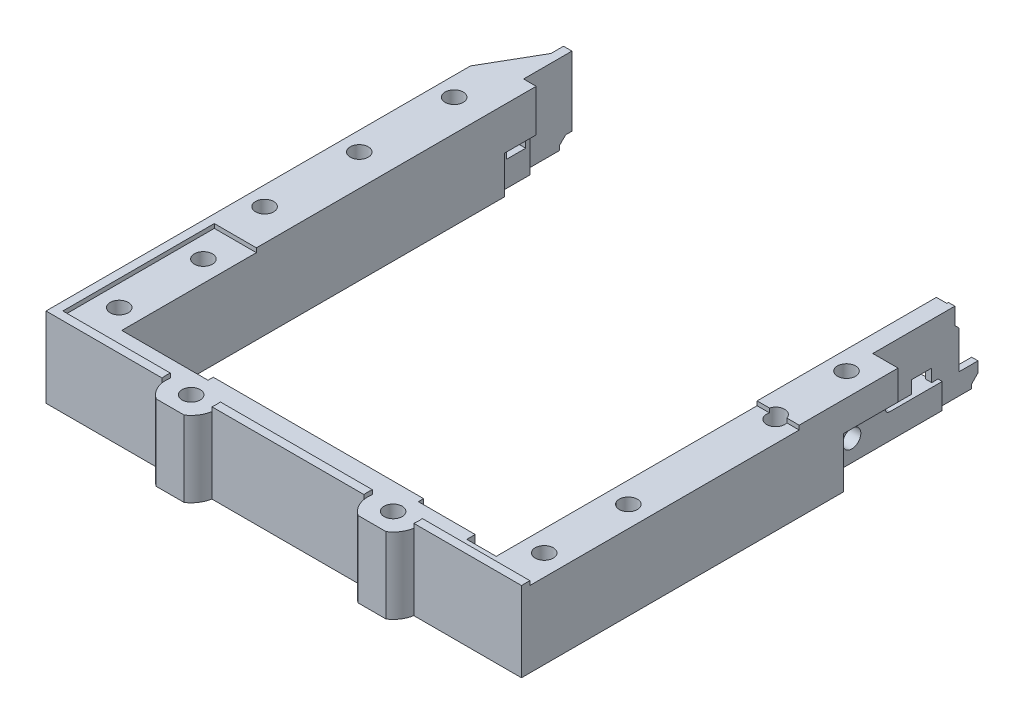
SolidWorks part; units mm, degrees
ref_plane "前视基准面" through (0, 0, 0) normal (0, 0, 1) x (1, 0, 0)
ref_plane "上视基准面" through (0, 0, 0) normal (0, 1, 0) x (1, 0, 0)
ref_plane "右视基准面" through (0, 0, 0) normal (1, 0, 0) x (0, 0, -1)
sketch "草图2" plane through (0, 0, 0) normal (0, 1, 0) x (1, 0, 0)
  line L0 (0, 0) -> (0, -10) construction
  line L1 (-45.5, 0) -> (45.5, 0)
  line L2 (45.5, 0) -> (45.5, 93)
  line L3 (45.5, 93) -> (55.5, 93)
  line L4 (55.5, 93) -> (55.5, -10)
  line L5 (55.5, -10) -> (-55.5, -10)
  line L6 (-45.5, 93) -> (-55.5, 93)
  line L7 (-55.5, 93) -> (-55.5, -10)
  line L8 (-45.5, 0) -> (-45.5, 93)
  dimension "D1" = 10
  dimension "D2" = 10
  dimension "D3" = 45.5
  dimension "D4" = 93
extrude "凸台-拉伸1" add sketch "草图2" along normal blind 18
sketch "草图3" plane through (0, 18, 0) normal (0, 1, 0) x (1, 0, 0)
  line L0 (55.5, 93) -> (45.5, 93) construction
  line L1 (45.5, 93) -> (45.5, 0) construction
  circle A0 centre (50, 76.75) radius 2.15
  dimension "D1" = 16.25
  dimension "D2" = 4.3
  dimension "D3" = 4.5
extrude "切除-拉伸1" cut sketch "草图3" against normal through all
sketch "草图4" plane through (55.5, 0, 0) normal (1, 0, 0) x (0, 0, -1)
  line L0 (-10, 0) -> (93, 0) construction
  line L1 (93, 18) -> (85.5, 18)
  line L2 (93, 18) -> (93, 0)
  line L3 (93, 0) -> (85.5, 0)
  line L4 (85.5, 18) -> (85.5, 0)
  line L5 (93, 18) -> (85.5, 0) construction
  line L6 (93, 0) -> (85.5, 18) construction
  point P4 (89.25, 9)
  dimension "D1" = 7.5
extrude "切除-拉伸2" cut sketch "草图4" against normal blind 6
sketch "草图5" plane through (55.5, 0, 0) normal (1, 0, 0) x (0, 0, -1)
  line L0 (85.5, 18) -> (85.5, 0) construction
  line L1 (85.5, 12) -> (70.5, 12)
  line L2 (85.5, 12) -> (85.5, 0)
  line L3 (85.5, 0) -> (70.5, 0)
  line L4 (70.5, 12) -> (70.5, 0)
  line L5 (85.5, 12) -> (70.5, 0) construction
  line L6 (85.5, 0) -> (70.5, 12) construction
  line L7 (-10, 0) -> (85.5, 0) construction
  line L8 (-10, 18) -> (85.5, 18) construction
  point P4 (78, 6)
  dimension "D1" = 6
  dimension "D2" = 15
extrude "切除-拉伸3" cut sketch "草图5" against normal up to surface (6 mm away) up to face at (49.5, 9, -89.25)
sketch "草图6" plane through (49.5, 0, 0) normal (1, 0, 0) x (0, 0, -1)
  line L1 (93, 0) -> (91, 0)
  line L2 (93, 0) -> (93, 9)
  line L3 (93, 9) -> (91, 9)
  line L4 (91, 0) -> (91, 9)
  line L5 (93, 0) -> (91, 9) construction
  line L6 (93, 9) -> (91, 0) construction
  point P4 (92, 4.5)
  dimension "D1" = 9
  dimension "D2" = 2
extrude "切除-拉伸4" cut sketch "草图6" against normal up to next
sketch "草图7" plane through (0, 18, 0) normal (0, 1, 0) x (1, 0, 0)
  line L0 (-45.5, 0) -> (-45.5, 93) construction
  line L1 (-55.5, 93) -> (-45.5, 93)
  line L2 (-55.5, 93) -> (-55.5, 32)
  line L3 (-55.5, 32) -> (-45.5, 32)
  line L4 (-45.5, 93) -> (-45.5, 32)
  line L5 (-55.5, 93) -> (-45.5, 32) construction
  line L6 (-55.5, 32) -> (-45.5, 93) construction
  point P4 (-50.5, 62.5)
  dimension "D1" = 61
extrude "凸台-拉伸2" add sketch "草图7" along normal blind 1
sketch "草图8" plane through (-55.5, 0, 0) normal (-1, 0, 0) x (0, 0, 1)
  line L1 (-32, 19) -> (-93, 19)
  line L2 (-32, 19) -> (-32, 0)
  line L3 (-32, 0) -> (-93, 0)
  line L4 (-93, 19) -> (-93, 0)
  line L5 (-32, 19) -> (-93, 0) construction
  line L6 (-32, 0) -> (-93, 19) construction
  point P4 (-62.5, 9.5)
extrude "凸台-拉伸3" add sketch "草图8" along normal blind 4
sketch "草图9" plane through (-55.5, 0, 0) normal (-1, 0, 0) x (0, 0, 1)
  line L1 (10, 0) -> (-32, 0)
  line L2 (10, 0) -> (10, 19)
  line L3 (10, 19) -> (-32, 19)
  line L4 (-32, 0) -> (-32, 19)
  line L5 (10, 0) -> (-32, 19) construction
  line L6 (10, 19) -> (-32, 0) construction
  point P4 (-11, 9.5)
extrude "凸台-拉伸4" add sketch "草图9" along normal blind 2
sketch "草图10" plane through (0, 18, 0) normal (0, 1, 0) x (1, 0, 0)
  line L0 (-57.5, -10) -> (-57.5, 32) construction
  line L1 (-55.5, -10) -> (55.5, -10) construction
  circle A0 centre (-50.5, 4.4) radius 2.15
  circle A1 centre (-50.5, 24.4) radius 2.15
  circle A2 centre (-24, -5) radius 2.15
  circle A3 centre (24, -5) radius 2.15
  dimension "D1" = 4.3
  dimension "D2" = 7
  dimension "D3" = 14.4
  dimension "D4" = 20
  dimension "D5" = 5
  dimension "D6" = 33.5
  dimension "D7" = 48
extrude "切除-拉伸5" cut sketch "草图10" against normal blind 6
sketch "草图11" plane through (0, 0, 0) normal (0, 0, -1) x (-1, 0, 0)
  line L0 (-45.5, 18) -> (45.5, 18) construction
  line L1 (-25, 18) -> (25, 18)
  line L2 (-25, 18) -> (-25, 0)
  line L3 (-25, 0) -> (25, 0)
  line L4 (25, 18) -> (25, 0)
  line L5 (-25, 18) -> (25, 0) construction
  line L6 (-25, 0) -> (25, 18) construction
  line L7 (-45.5, 0) -> (45.5, 0) construction
  point P4 (0, 9)
  dimension "D1" = 50
extrude "凸台-拉伸5" add sketch "草图11" along normal blind 1.25
sketch "草图12" plane through (0, 18, 0) normal (0, 1, 0) x (1, 0, 0)
  line L0 (49.5, 93) -> (45.5, 93)
  line L1 (45.5, 93) -> (45.5, 60)
  line L2 (45.5, 93) -> (45.5, 0) construction
  line L3 (45.5, 60) -> (55.5, 60)
  line L4 (55.5, -10) -> (55.5, 85.5) construction
  line L5 (55.5, 60) -> (55.5, 85.5)
  line L6 (55.5, 85.5) -> (49.5, 85.5)
  line L7 (49.5, 85.5) -> (49.5, 93)
  circle A0 centre (50, 76.75) radius 2.15 construction
  circle A1 centre (50, 76.75) radius 2.15
  dimension "D1" = 33
extrude "凸台-拉伸6" add sketch "草图12" along normal blind 1
sketch "草图13" plane through (0, 18, 0) normal (0, 1, 0) x (1, 0, 0)
  line L1 (45.5, 0) -> (38.5, 0)
  line L2 (45.5, 0) -> (45.5, -2)
  line L3 (45.5, -2) -> (38.5, -2)
  line L4 (38.5, 0) -> (38.5, -2)
  line L5 (45.5, 0) -> (38.5, -2) construction
  line L6 (45.5, -2) -> (38.5, 0) construction
  point P4 (42, -1)
  dimension "D1" = 7
  dimension "D2" = 2
extrude "切除-拉伸6" cut sketch "草图13" against normal up to surface (18 mm away) up to face at (4.075, 0, -39.3889)
sketch "草图14" plane through (0, 18, 0) normal (0, 1, 0) x (1, 0, 0)
  line L0 (55.5, -10) -> (55.5, 60) construction
  line L1 (-57.5, -10) -> (-27.3166, -10)
  line L2 (-57.5, -10) -> (-57.5, -6)
  line L3 (-57.5, -6) -> (-29.9161, -6)
  line L4 (55.5, -10) -> (55.5, -6)
  line L5 (-18.0839, -6) -> (18.0839, -6)
  line L6 (-20.6834, -10) -> (20.6834, -10)
  line L7 (29.9161, -6) -> (55.5, -6)
  line L8 (27.3166, -10) -> (55.5, -10)
  arc A0 (-29.9161, -6) -> (-27.3166, -10) centre (-24, -5) ccw
  arc A1 (18.0839, -6) -> (20.6834, -10) centre (24, -5) ccw
  arc A2 (-20.6834, -10) -> (-18.0839, -6) centre (-24, -5) ccw
  arc A3 (27.3166, -10) -> (29.9161, -6) centre (24, -5) ccw
  dimension "D2" = 12
  dimension "D3" = 12
  dimension "D1" = 4
extrude "切除-拉伸7" cut sketch "草图14" against normal through all and the other way through all
sketch "草图16" plane through (0, 18, 0) normal (0, 1, 0) x (1, 0, 0)
  line L0 (55.5, -6) -> (55.5, 60) construction
  line L1 (-55.5, -6) -> (-29.9161, -6)
  line L2 (-55.5, -6) -> (-55.5, -4)
  line L3 (-55.5, -4) -> (-29.9161, -4)
  line L4 (55.5, -6) -> (55.5, -4)
  line L5 (-18.0839, -4) -> (18.0839, -4)
  line L6 (-18.0839, -6) -> (18.0839, -6)
  line L7 (29.9161, -4) -> (55.5, -4)
  line L8 (29.9161, -6) -> (55.5, -6)
  arc A0 (-29.9161, -4) -> (-29.9161, -6) centre (-24, -5) ccw
  arc A1 (18.0839, -4) -> (18.0839, -6) centre (24, -5) ccw
  arc A2 (-18.0839, -6) -> (-18.0839, -4) centre (-24, -5) ccw
  arc A3 (29.9161, -6) -> (29.9161, -4) centre (24, -5) ccw
  dimension "D1" = 2
extrude "凸台-拉伸7" add sketch "草图16" along normal up to surface (1 mm away) up to face at (-54.5, 19, -37.75)
sketch "草图18" plane through (0, 19, 0) normal (0, 1, 0) x (1, 0, 0)
  line L0 (-53, 86.45) -> (-53, 41.45) construction
  line L1 (-59.5, 32) -> (-59.5, 93) construction
  line L2 (-45.5, 93) -> (-59.5, 93) construction
  circle A0 centre (-53, 86.45) radius 2.15
  circle A1 centre (-53, 63.95) radius 2.15
  circle A2 centre (-53, 41.45) radius 2.15
  dimension "D1" = 4.3
  dimension "D2" = 6.5
  dimension "D3" = 6.55
  dimension "D4" = 45
extrude "切除-拉伸8" cut sketch "草图18" against normal blind 6
sketch "草图19" plane through (0, 12, 0) normal (0, 1, 0) x (1, 0, 0)
  circle A0 centre (24, -5) radius 2.15 construction
  circle A1 centre (-24, -5) radius 2.15 construction
  circle A2 centre (24, -5) radius 2.15
  circle A3 centre (-24, -5) radius 2.15
extrude "切除-拉伸9" cut sketch "草图19" against normal through all
sketch "草图20" plane through (0, 13, 0) normal (0, 1, 0) x (1, 0, 0)
  line L0 (0, 0) -> (0, 86.45) construction
  circle A0 centre (-50.5, 4.4) radius 2.15 construction
  circle A1 centre (-50.5, 24.4) radius 2.15 construction
  circle A2 centre (-53, 41.45) radius 2.15 construction
  circle A3 centre (-53, 63.95) radius 2.15 construction
  circle A4 centre (-53, 86.45) radius 2.15 construction
  circle A5 centre (-50.5, 4.4) radius 2.15
  circle A6 centre (-50.5, 24.4) radius 2.15
  circle A7 centre (-53, 41.45) radius 2.15
  circle A8 centre (-53, 63.95) radius 2.15
  circle A9 centre (-53, 86.45) radius 2.15
  circle A10 centre (50.5, 24.4) radius 2.15
  circle A11 centre (50.5, 4.4) radius 2.15
extrude "切除-拉伸10" cut sketch "草图20" against normal through all and the other way through all
sketch "草图21" plane through (0, 0, 0) normal (0, -1, 0) x (1, 0, 0)
  line L1 (-45.5, -93) -> (45.5, -93)
  line L2 (-45.5, -93) -> (-45.5, 2)
  line L3 (-45.5, 2) -> (45.5, 2)
  line L4 (45.5, -93) -> (45.5, 2)
extrude "凸台-拉伸8" [suppressed] add sketch "草图21" against normal blind 2
sketch "草图22" [suppressed] plane through (0, 2, 0) normal (0, 1, 0) x (1, 0, 0)
  line L1 (38.5, 0) -> (45.5, 0)
  line L2 (38.5, 0) -> (38.5, -2)
  line L3 (38.5, -2) -> (45.5, -2)
  line L4 (45.5, 0) -> (45.5, -2)
extrude "凸台-拉伸9" [suppressed] add sketch "草图22" along normal blind 15
sketch "草图23" plane through (0, 0, -32) normal (0, 0, 1) x (1, 0, 0)
  line L4 (-59.5, 0) -> (-57.5, 0)
  line L5 (-57.5, 0) -> (-57.5, 19)
  line L6 (-57.5, 19) -> (-59.5, 19)
  line L7 (-59.5, 19) -> (-59.5, 0)
  line L8 (-59.5, 0) -> (-57.5, 0)
  line L9 (-57.5, 0) -> (-57.5, 19)
  line L10 (-57.5, 19) -> (-59.5, 19)
  line L11 (-59.5, 19) -> (-59.5, 0)
  dimension "D1" = 0
extrude "切除-拉伸11" cut sketch "草图23" against normal through all
sketch "草图24" plane through (0, 19, 0) normal (0, 1, 0) x (1, 0, 0)
  line L0 (-45.5, 93) -> (-49.5, 93)
  line L1 (-45.5, 93) -> (-57.5, 93) construction
  line L2 (-49.5, 93) -> (-45.5, 89)
  line L3 (-45.5, 32) -> (-45.5, 93) construction
  line L4 (-45.5, 89) -> (-45.5, 93)
  dimension "D1" = 4
  dimension "D2" = 4
sketch "草图26" plane through (49.5, 0, 0) normal (1, 0, 0) x (0, 0, -1)
  line L0 (91, 0) -> (91, 6)
  line L2 (91, 9) -> (91, 0) construction
  line L3 (91, 6) -> (98, 6)
  line L4 (98, 6) -> (98, 9)
  line L5 (98, 9) -> (93, 9)
  line L6 (93, 9) -> (93, 19)
  line L7 (93, 19) -> (107, 19)
  line L8 (107, 19) -> (107, 0)
  line L9 (107, 0) -> (91, 0)
  dimension "D1" = 6
  dimension "D2" = 5
  dimension "D3" = 16
extrude "凸台-拉伸10" add sketch "草图26" against normal offset from surface (3 mm away) 1 contours L8 L9 L0 L3 L4 L5 L6 L7 up to face at (45.5, 11.5, -60.5)
sketch "草图27" plane through (46.5, 0, 0) normal (-1, 0, 0) x (0, 0, 1)
  line L0 (-98, 13) -> (-98, 0)
  line L1 (-91, 0) -> (-107, 0) construction
  line L2 (-98, 0) -> (-107, 0)
  line L3 (-107, 0) -> (-107, 19)
  line L4 (-98, 9) -> (-98, 6) construction
  line L5 (-93, 9) -> (-98, 9) construction
  line L6 (-98, 13) -> (-101.4641, 19)
  line L7 (-107, 19) -> (-93, 19) construction
  line L8 (-107, 19) -> (-101.4641, 19)
  dimension "D1" = 4
  dimension "D2" = 150
extrude "切除-拉伸13" cut sketch "草图27" against normal offset from surface (1.5 mm away) 2.5 up to face at (45.5, 11.5, -60.5)
sketch "草图28" plane through (46.5, 0, 0) normal (-1, 0, 0) x (0, 0, 1)
  line L5 (-101.4641, 19) -> (-98, 13)
  line L6 (-98, 13) -> (-98, 9)
  line L7 (-98, 9) -> (-93, 9)
  line L8 (-93, 9) -> (-93, 19)
  line L9 (-93, 19) -> (-101.4641, 19)
  line L10 (-101.4641, 19) -> (-98, 13)
  line L11 (-98, 13) -> (-98, 9)
  line L12 (-98, 9) -> (-93, 9)
  line L13 (-93, 9) -> (-93, 19)
  line L14 (-93, 19) -> (-101.4641, 19)
  dimension "D1" = 0
extrude "凸台-拉伸11" add sketch "草图28" along normal up to surface (1 mm away) up to face at (45.5, 11.5, -60.5)
sketch "草图29" plane through (49.5, 0, 0) normal (1, 0, 0) x (0, 0, -1)
  line L0 (85.5, 12) -> (85.5, 6)
  line L1 (85.5, 6) -> (99, 6)
  line L3 (99, 6) -> (99, 0)
  line L4 (99, 0) -> (78.8411, 0)
  line L5 (70.5, 0) -> (70.5, 12)
  line L6 (70.5, 12) -> (74.6589, 12)
  line L7 (98, 6) -> (98, 9) construction
  line L8 (91, 6) -> (98, 6) construction
  line L9 (78.8411, 12) -> (78.8411, 0)
  line L10 (78.8411, 0) -> (78.8411, 12) construction
  line L11 (74.6589, 0) -> (74.6589, 12)
  line L12 (78.8411, 12) -> (85.5, 12)
  line L13 (74.6589, 0) -> (70.5, 0)
  dimension "D1" = 1
extrude "凸台-拉伸12" add sketch "草图29" along normal offset from surface (1 mm away) 5 up to face at (45.5, 11.6667, -66.1627)
fillet "圆角1" radius 1 1 edges at (50, 6, -85.5)
sketch "草图30" plane through (49.5, 0, 0) normal (1, 0, 0) x (0, 0, -1)
  line L2 (107, 19) -> (107, 0) construction
  line L3 (107, 11) -> (107, 19)
  line L4 (107, 19) -> (101.5, 19)
  line L6 (107, 11) -> (102.5, 11)
  line L7 (101.5, 12) -> (101.5, 19)
  line L8 (85.5, 19) -> (85.5, 12) construction
  arc A0 (102.5, 11) -> (101.5, 12) centre (102.5, 12) cw
  dimension "D2" = 1
  dimension "D1" = 8
  dimension "D3" = 16
extrude "切除-拉伸14" cut sketch "草图30" against normal up to next
sketch "草图31" plane through (49.5, 0, 0) normal (1, 0, 0) x (0, 0, -1)
  line L0 (107, 1) -> (108.5, 2.5)
  line L1 (107, 11) -> (107, 0) construction
  line L2 (108.5, 2.5) -> (108.5, 11)
  line L3 (108.5, 11) -> (107, 11)
  line L6 (99, 0) -> (107, 0) construction
  line L8 (107, 11) -> (107, 1)
  dimension "D1" = 1.5
  dimension "D2" = 1
  dimension "D3" = 45
extrude "凸台-拉伸13" add sketch "草图31" against normal up to surface (1.5 mm away) up to face at (48, 9.9793, -101.2757)
sketch "草图32" plane through (49.5, 0, 0) normal (1, 0, 0) x (0, 0, -1)
  line L0 (99, 6) -> (86.5, 6) construction
  line L1 (91, 9) -> (92.75, 9)
  line L2 (91, 9) -> (91, 6)
  line L3 (91, 6) -> (92.75, 6)
  line L4 (92.75, 9) -> (92.75, 6)
  dimension "D1" = 1.75
extrude "凸台-拉伸14" add sketch "草图32" against normal up to surface (4 mm away) up to face at (45.5, 11.6667, -66.1627)
chamfer "倒角1" distance 1 angle 60 1 edges at (45.5, 6, -91.875) first distance on face at (46, 6, -91.875)
sketch "草图33" plane through (0, 19, 0) normal (0, 1, 0) x (1, 0, 0)
  circle A0 centre (-53, 86.45) radius 2.15
  circle A1 centre (-53, 86.45) radius 2.15 construction
extrude "凸台-拉伸16" add sketch "草图33" against normal up to surface (19 mm away) up to face at (19.4221, 0, -39.5712)
sketch "草图34" plane through (0, 19, 0) normal (0, 1, 0) x (1, 0, 0)
  line L1 (-45.5, 93) -> (-57.5, 93) construction
  line L2 (-53, 86.5) -> (-53, 63.95) construction
  circle A0 centre (-53, 86.5) radius 2.15
  circle A1 centre (-53, 63.95) radius 2.15 construction
  dimension "D2" = 6.5
extrude "切除-拉伸15" cut sketch "草图34" against normal up to next
sketch "草图35" plane through (0, 19, 0) normal (0, 1, 0) x (1, 0, 0)
  circle A0 centre (-53, 86.5) radius 5
  circle A1 centre (-53, 86.5) radius 2.15
  circle A2 centre (-53, 86.5) radius 2.15 construction
  dimension "D1" = 10
sketch "草图36" plane through (-57.5, 0, 0) normal (-1, 0, 0) x (0, 0, 1)
  line L0 (-93, 6) -> (-98.5, 6)
  line L1 (-93, 0) -> (-93, 19) construction
  line L2 (-98.5, 6) -> (-98.5, 9)
  line L3 (-98.5, 9) -> (-93, 9)
  line L4 (-91, 0) -> (-98, 0) construction
  line L5 (-92.75, 9) -> (-98, 9) construction
  line L6 (-93, 6) -> (-93, 0)
  line L7 (-93, 0) -> (-107, 0)
  line L8 (-107, 0) -> (-98, 0) construction
  line L9 (-93, 0) -> (6, 0) construction
  line L10 (-107, 0) -> (-107, 1)
  line L11 (-107, 1) -> (-108.5, 2.5)
  line L12 (-108.5, 2.5) -> (-110, 2.5)
  line L13 (-110, 2.5) -> (-110, 19)
  line L14 (-110, 19) -> (-93, 19)
  line L15 (-93, 19) -> (-93, 9)
  dimension "D1" = 5.5
  dimension "D2" = 6
  dimension "D3" = 14
  dimension "D4" = 1.5
extrude "凸台-拉伸18" add sketch "草图36" against normal up to surface (12 mm away) up to face at (-45.5, 12.3333, -41.6667)
sketch "草图38" plane through (0, 0, -92.75) normal (0, 0, -1) x (-1, 0, 0)
  line L0 (-46.5, 6) -> (-46.5, 8)
  line L1 (-46.5, 8) -> (-45.5, 9)
  line L2 (-45.5, 0) -> (-45.5, 18) construction
  line L3 (-45.5, 9) -> (-45.5, 6)
  line L4 (-45.5, 6) -> (-46.5, 6)
  dimension "D1" = 45
extrude "切除-拉伸16" cut sketch "草图38" against normal up to surface (1.75 mm away) up to face at (46, 3.433, -91)
sketch "草图39" plane through (-45.5, 0, 0) normal (1, 0, 0) x (0, 0, -1)
  line L0 (110, 2.5) -> (110, 19) construction
  line L1 (91, 9) -> (110, 9)
  line L2 (91, 9) -> (91, 0)
  line L3 (91, 0) -> (110, 0)
  line L4 (110, 9) -> (110, 0)
  line L5 (0, 0) -> (107, 0) construction
  line L6 (93, 9) -> (98.5, 9) construction
  line L7 (93, 9) -> (93, 6) construction
  dimension "D1" = 2
extrude "切除-拉伸17" cut sketch "草图39" against normal blind 1.5
chamfer "倒角2" distance 1.5 angle 45 1 edges at (-47, 9, -92)
sketch "草图40" plane through (-47, 0, 0) normal (1, 0, 0) x (0, 0, -1)
  line L0 (32, 19) -> (110, 19) construction
  line L1 (98.5, 19) -> (110, 19)
  line L2 (98.5, 19) -> (98.5, 0)
  line L3 (98.5, 0) -> (110, 0)
  line L4 (110, 19) -> (110, 0)
  line L5 (110, 9) -> (110, 19) construction
  line L7 (91, 0) -> (107, 0) construction
  line L8 (98.5, 6) -> (98.5, 9) construction
extrude "切除-拉伸18" cut sketch "草图40" against normal blind 1.5 and the other way blind 1.5
sketch "草图41" plane through (-57.5, 0, 0) normal (-1, 0, 0) x (0, 0, 1)
  line L0 (-107, 19) -> (-107, 0)
  line L1 (6, 19) -> (-110, 19) construction
  line L2 (-107, 0) -> (6, 0) construction
  line L3 (-93, 6) -> (-93, 7.5) construction
  line L4 (-107, 19) -> (-110, 19)
  line L5 (-110, 19) -> (-110, 2.5)
  line L6 (-110, 2.5) -> (-107, 0)
  dimension "D1" = 14
extrude "切除-拉伸19" cut sketch "草图41" against normal blind 7
chamfer "倒角3" distance 7 angle 60 1 edges at (-57.5, 9.5, -107) first distance on face at (-52.1667, 6.6667, -107)
sketch "草图42" plane through (0, 9, 0) normal (0, -1, 0) x (1, 0, 0)
  line L1 (-51.5, -93) -> (-51.5, -105.2679)
  line L2 (-57.5, -94.8756) -> (-50.5, -107) construction
  line L3 (-51.5, -105.2679) -> (-57.5, -94.8756)
  line L4 (-48.5, -98.5) -> (-48.5, -107) construction
  line L8 (-57.5, -94.8756) -> (-57.5, -93)
  line L9 (-57.5, -93) -> (-51.5, -93)
  line L10 (-45.5, -93) -> (-57.5, -93) construction
  dimension "D1" = 3
extrude "切除-拉伸20" cut sketch "草图42" along normal up to next
sketch "草图43" plane through (49.5, 0, 0) normal (1, 0, 0) x (0, 0, -1)
  line L0 (104, 23.9473) -> (104, -7.2516) construction
  line L1 (98, 6) -> (98, 9) construction
  line L2 (108.5, 2.5) -> (108.5, 11) construction
  line L3 (104, 11) -> (108.5, 11)
  line L4 (104, 11) -> (104, 4)
  line L5 (104, 4) -> (108.5, 4)
  line L6 (108.5, 11) -> (108.5, 4)
  line L7 (102.5, 11) -> (108.5, 11) construction
  line L8 (99, 6) -> (86.5, 6) construction
  dimension "D1" = 6
  dimension "D2" = 2
extrude "切除-拉伸21" cut sketch "草图43" against normal blind 0.7
fillet "圆角2" radius 2 1 edges at (49.15, 4, -104)
sketch "草图44" plane through (48.8, 0, 0) normal (1, 0, 0) x (0, 0, -1)
  line L0 (108.5, 5) -> (104, 5)
  line L1 (108.5, 4) -> (108.5, 11) construction
  line L2 (104, 11) -> (104, 6) construction
  line L3 (108.5, 11) -> (104, 11) construction
  line L4 (108.5, 5) -> (108.5, 11)
  line L5 (104, 11) -> (104, 6)
  line L6 (108.5, 11) -> (104, 11)
  line L7 (106, 4) -> (108.5, 4) construction
  line L8 (104, 6) -> (104, 5)
  dimension "D1" = 1
extrude "切除-拉伸22" cut sketch "草图44" against normal up to next and the other way up to next
sketch "草图45" plane through (48.8, 0, 0) normal (1, 0, 0) x (0, 0, -1)
  line L3 (108.5, 5) -> (104.2679, 5)
  line L4 (106, 4) -> (108.5, 4)
  line L5 (108.5, 4) -> (108.5, 5)
  line L6 (108.5, 5) -> (104.2679, 5)
  line L7 (106, 4) -> (108.5, 4)
  line L8 (108.5, 4) -> (108.5, 5)
  arc A1 (104.2679, 5) -> (106, 4) centre (106, 6) ccw
  arc A2 (104.2679, 5) -> (106, 4) centre (106, 6) ccw
  dimension "D1" = 0
extrude "凸台-拉伸19" add sketch "草图45" along normal up to surface (0.7 mm away) up to face at (49.5, 7.0927, -99.561)
sketch "草图46" plane through (49.5, 0, 0) normal (1, 0, 0) x (0, 0, -1)
  line L0 (99, 6) -> (86.5, 6) construction
  line L1 (98, 9) -> (97.5, 9)
  line L2 (98, 9) -> (98, 6)
  line L3 (98, 6) -> (97.5, 6)
  line L4 (97.5, 9) -> (97.5, 6)
  dimension "D1" = 0.5
extrude "凸台-拉伸20" add sketch "草图46" against normal up to surface (1.5 mm away) up to face at (48, 8.0923, -102.6969)
sketch "草图47" plane through (-51.5, 0, 0) normal (-1, 0, 0) x (0, 0, 1)
  line L1 (-98.5, 9) -> (-97.5, 9)
  line L2 (-98.5, 9) -> (-98.5, 6)
  line L3 (-98.5, 6) -> (-97.5, 6)
  line L4 (-97.5, 9) -> (-97.5, 6)
extrude "凸台-拉伸21" add sketch "草图47" against normal up to surface (4.5 mm away) up to face at (-47, 4.5, -94.1667)
sketch "草图48" plane through (49.5, 0, 0) normal (1, 0, 0) x (0, 0, -1)
  line L0 (85.5, 7) -> (85.5, 12) construction
  line L1 (85.5, 8) -> (83.5, 8)
  line L2 (85.5, 8) -> (85.5, 19)
  line L3 (85.5, 19) -> (83.5, 19)
  line L4 (83.5, 8) -> (83.5, 19)
  line L5 (60, 19) -> (85.5, 19) construction
  line L6 (92.75, 6) -> (86.5, 6) construction
  dimension "D1" = 2
  dimension "D2" = 2
extrude "切除-拉伸23" cut sketch "草图48" along normal up to next
fillet "圆角3" radius 0.5 2 edges at (50, 8, -85.5) (50, 8, -83.5)
sketch "草图49" plane through (48, 0, 0) normal (-1, 0, 0) x (0, 0, 1)
  line L0 (-98, 11) -> (-102.6188, 19)
  line L1 (-98, 9) -> (-98, 13) construction
  line L2 (-102.6188, 19) -> (-101.4641, 19)
  line L3 (-101.4641, 19) -> (-98, 13)
  line L4 (-98, 13) -> (-98, 11)
  dimension "D1" = 1
extrude "凸台-拉伸22" add sketch "草图49" along normal up to surface (2.5 mm away) up to face at (45.5, 11.4, -68.8214)
sketch "草图50" plane through (49.5, 0, 0) normal (1, 0, 0) x (0, 0, -1)
  line L1 (104, 11) -> (101.5, 11)
  line L2 (104, 11) -> (104, 19)
  line L3 (104, 19) -> (101.5, 19)
  line L4 (101.5, 11) -> (101.5, 19)
extrude "凸台-拉伸23" add sketch "草图50" against normal up to surface (1.5 mm away) up to face at (48, 7.0237, -102.0862)
sketch "草图51" plane through (48, 0, 0) normal (-1, 0, 0) x (0, 0, 1)
  line L1 (-104, 19) -> (-103, 19)
  line L2 (-104, 19) -> (-104, 14)
  line L3 (-104, 14) -> (-103, 14)
  line L4 (-103, 19) -> (-103, 14)
  dimension "D1" = 1
  dimension "D2" = 5
extrude "切除-拉伸24" cut sketch "草图51" against normal up to next
chamfer "倒角4" distance 1 angle 45 1 edges at (48.75, 14, -103)
sketch "草图52" plane through (0, 0, 0) normal (0, -1, 0) x (1, 0, 0)
  line L0 (50.5, -73.792) -> (50.5, -79.708)
  line L1 (50.5, -70.5) -> (50.5, -74.6589) construction
  line L2 (50.5, -83.5) -> (50.5, -78.8411) construction
  arc A0 (50.5, -73.792) -> (50.5, -79.708) centre (50, -76.75) ccw
  dimension "D1" = 6
extrude "凸台-拉伸25" add sketch "草图52" against normal up to surface (12 mm away) up to face at (52.4417, 12, -76.9167)
sketch "草图53" plane through (50.5, 0, 0) normal (1, 0, 0) x (0, 0, -1)
  line L0 (77.5, 12) -> (77.5, 0) construction
  line L1 (83.5, 12) -> (70.5, 12) construction
  line L2 (70.5, 0) -> (99, 0) construction
  line L3 (70.5, 12) -> (70.5, 0) construction
  circle A0 centre (77.5, 5) radius 2.15
  dimension "D1" = 4.3
  dimension "D3" = 5
  dimension "D2" = 7
extrude "切除-拉伸25" cut sketch "草图53" against normal up to next
sketch "草图54" plane through (0, 0, 0) normal (0, -1, 0) x (1, 0, 0)
  line L0 (50.5, -24.4) -> (50.5, -59.4) construction
  circle A0 centre (50.5, -59.4) radius 2.15
  dimension "D1" = 4.3
  dimension "D2" = 35
extrude "切除-拉伸26" cut sketch "草图54" against normal up to next
equation "\"1、\"=4"
